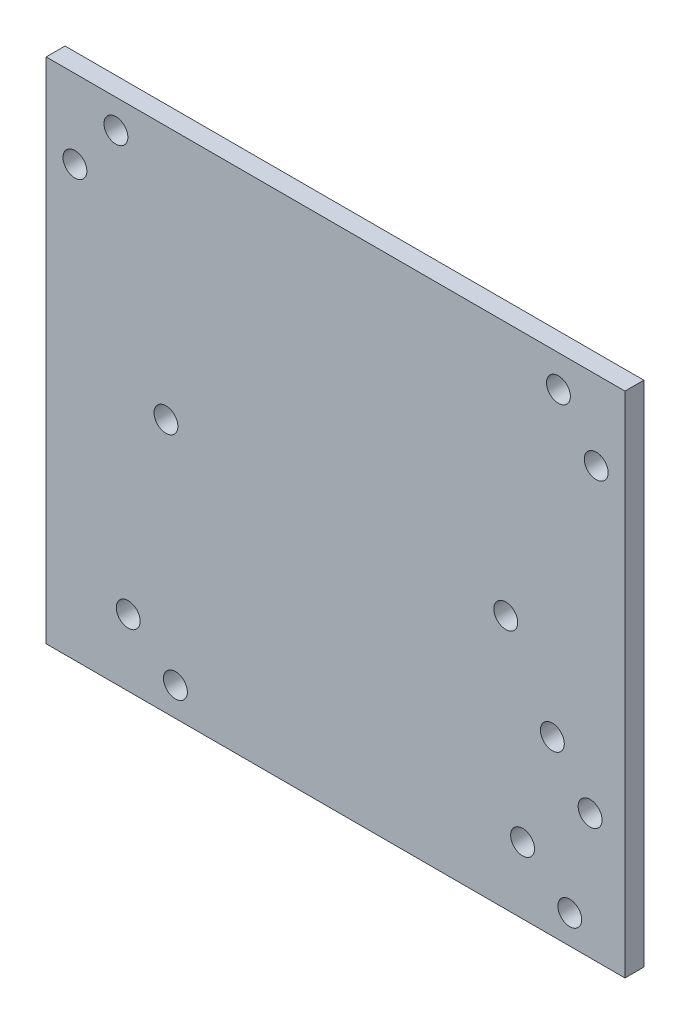
SolidWorks part; units mm, degrees
ref_plane "Front Plane" through (0, 0, 0) normal (0, 0, 1) x (1, 0, 0)
ref_plane "Top Plane" through (0, 0, 0) normal (0, 1, 0) x (1, 0, 0)
ref_plane "Right Plane" through (0, 0, 0) normal (1, 0, 0) x (0, 0, -1)
sketch "Sketch1" plane through (0, 0, 0) normal (0, 0, 1) x (1, 0, 0)
  line L0 (959.4886, 308.695) -> (959.4886, 257.3944) construction
  line L1 (959.4886, 234.6614) -> (959.4886, 406.5207) construction
  line L2 (862.0448, 217.2783) -> (1056.7178, 217.2783)
  line L3 (862.0448, 217.2783) -> (862.0448, 388.2332)
  line L4 (862.0448, 388.2332) -> (1056.7178, 388.2332)
  line L5 (1056.7178, 217.2783) -> (1056.7178, 388.2332)
  line L6 (902.3386, 302.7557) -> (1016.6386, 302.7557) construction
  circle A0 centre (1022.28, 239.6533) radius 2.5273 construction
  circle A1 centre (1038.155, 226.9533) radius 2.5273 construction
  circle A2 centre (889.6448, 239.6533) radius 2.5273 construction
  circle A3 centre (1034.3339, 377.4809) radius 2.5273 construction
  circle A4 centre (1047.0428, 361.6131) radius 2.5273 construction
  circle A5 centre (871.7198, 361.7933) radius 2.5273 construction
  circle A6 centre (885.5053, 378.5582) radius 2.5273 construction
  circle A7 centre (1022.28, 239.6533) radius 2.5273 construction
  circle A8 centre (1038.155, 226.9533) radius 2.5273 construction
  circle A9 centre (889.6448, 239.6533) radius 2.5273 construction
  circle A10 centre (1034.3339, 377.4809) radius 2.5273 construction
  circle A11 centre (1047.0428, 361.6131) radius 2.5273 construction
  circle A12 centre (871.7198, 361.7933) radius 2.5273 construction
  circle A13 centre (885.5053, 378.5582) radius 2.5273 construction
  circle A14 centre (905.5198, 226.9533) radius 2.5273 construction
  circle A15 centre (905.5198, 226.9533) radius 2.5273 construction
  circle A16 centre (1022.28, 239.6533) radius 4.0127
  circle A17 centre (1038.155, 226.9533) radius 4.0127
  circle A18 centre (889.6448, 239.6533) radius 4.0127
  circle A19 centre (1034.3339, 377.4809) radius 4.0127
  circle A20 centre (1047.0428, 361.6131) radius 4.0127
  circle A21 centre (871.7198, 361.7933) radius 4.0127
  circle A22 centre (885.5053, 378.5582) radius 4.0127
  circle A23 centre (905.5198, 226.9533) radius 4.0127
  circle A24 centre (885.5053, 378.5582) radius 6.5 construction
  circle A25 centre (871.7198, 361.7933) radius 6.5 construction
  circle A26 centre (889.6448, 239.6533) radius 6.5 construction
  circle A27 centre (905.5198, 226.9533) radius 6.5 construction
  circle A28 centre (1022.28, 239.6533) radius 6.5 construction
  circle A29 centre (1038.155, 226.9533) radius 6.5 construction
  circle A30 centre (1047.0428, 361.6131) radius 6.5 construction
  circle A31 centre (1034.3339, 377.4809) radius 6.5 construction
  circle A32 centre (-682.1218, 370.9328) radius 4.0127 construction
  circle A33 centre (902.3386, 302.7557) radius 4.0127
  circle A34 centre (-672.6612, 301.2062) radius 4.0132 construction
  circle A35 centre (-672.6612, 301.2062) radius 4.0132 construction
  circle A36 centre (1016.6386, 302.7557) radius 4.0127
  circle A37 centre (1044.9866, 259.4145) radius 2.5273 construction
  circle A38 centre (1032.2866, 275.2895) radius 2.5273 construction
  circle A39 centre (1044.9866, 259.4145) radius 2.5273 construction
  circle A40 centre (1032.2866, 275.2895) radius 2.5273 construction
  circle A41 centre (1032.2866, 275.2895) radius 4.0254
  circle A42 centre (1044.9866, 259.4145) radius 4.0254
  point P60 (959.4886, 302.7557)
  point P76 (862.0448, 302.7557)
  dimension "D2" = 114.3
  dimension "D1" = 13
  dimension "D3" = 3.175
  dimension "D4" = 3.175
  dimension "D5" = 3.175
  dimension "D6" = 3.175
  dimension "D7" = 8.0508
extrude "Boss-Extrude1" add sketch "Sketch1" along normal blind 6.35
